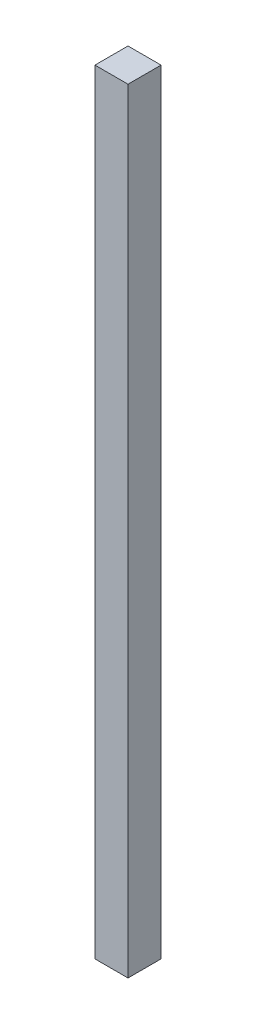
SolidWorks part; units mm, degrees
ref_plane "Front Plane" through (0, 0, 0) normal (0, 0, 1) x (1, 0, 0)
ref_plane "Top Plane" through (0, 0, 0) normal (0, 1, 0) x (1, 0, 0)
ref_plane "Right Plane" through (0, 0, 0) normal (1, 0, 0) x (0, 0, -1)
sketch "Sketch1" plane through (0, 0, 0) normal (0, 1, 0) x (1, 0, 0)
  line L1 (0, 0) -> (25.4, 0)
  line L2 (0, 0) -> (0, 25.4)
  line L3 (0, 25.4) -> (25.4, 25.4)
  line L4 (25.4, 0) -> (25.4, 25.4)
  dimension "D1" = 25.4
  dimension "D2" = 25.4
extrude "Boss-Extrude1" add sketch "Sketch1" along normal blind 609.6
sketch "Sketch3" plane through (0, 0, -25.4) normal (0, 0, -1) x (-1, 0, 0)
  line L0 (0, 609.6) -> (0, 0) construction
  line L1 (0, 484.3268) -> (-25.4, 484.3268)
  line L2 (0, 484.3268) -> (0, 609.6)
  line L3 (0, 609.6) -> (-25.4, 609.6)
  line L4 (-25.4, 484.3268) -> (-25.4, 609.6)
  line L5 (0, 484.3268) -> (-25.4, 484.3268) construction
extrude "Cut-Extrude1" [suppressed] cut sketch "Sketch3" against normal up to surface (25.4 mm away) up to face at (12.7, 304.8, 0)
sketch "Sketch4" [suppressed] plane through (0, 0, 0) normal (0, 0, 1) x (1, 0, 0)
  line L0 (0, 609.6) -> (0, 0) construction
  line L1 (0, 297.6179) -> (25.4, 297.6179)
  line L2 (0, 297.6179) -> (0, 609.6)
  line L3 (0, 609.6) -> (25.4, 609.6)
  line L4 (25.4, 297.6179) -> (25.4, 609.6)
  line L5 (25.4, 297.6179) -> (0, 297.6179) construction
extrude "Cut-Extrude2" [suppressed] cut sketch "Sketch4" against normal up to surface (25.4 mm away) up to face at (12.7, 304.8, -25.4)
sketch "Sketch5" plane through (0, 0, -25.4) normal (0, 0, -1) x (-1, 0, 0)
  line L0 (0, 609.6) -> (0, 0) construction
  line L1 (0, 594.529) -> (-25.4, 594.529)
  line L2 (0, 594.529) -> (0, 609.6)
  line L3 (0, 609.6) -> (-25.4, 609.6)
  line L4 (-25.4, 594.529) -> (-25.4, 609.6)
  line L5 (0, 594.529) -> (-25.4, 594.529) construction
extrude "Cut-Extrude3" cut sketch "Sketch5" against normal up to surface (25.4 mm away) up to face at (12.7, 304.8, 0)
sketch "Sketch6" [suppressed] plane through (0, 0, -25.4) normal (0, 0, -1) x (-1, 0, 0)
  line L0 (0, 609.6) -> (0, 0) construction
  line L1 (0, 574.651) -> (-25.4, 574.651)
  line L2 (0, 574.651) -> (0, 609.6)
  line L3 (0, 609.6) -> (-25.4, 609.6)
  line L4 (-25.4, 574.651) -> (-25.4, 609.6)
  line L5 (0, 574.651) -> (-25.4, 574.651) construction
extrude "Cut-Extrude4" [suppressed] cut sketch "Sketch6" against normal up to surface (25.4 mm away) up to face at (12.7, 297.2645, 0)
sketch "Sketch7" [suppressed] plane through (0, 0, 0) normal (0, 0, 1) x (1, 0, 0)
  line L0 (25.4, 609.6) -> (25.4, 0) construction
  line L1 (25.4, 443.1645) -> (0, 443.1645)
  line L2 (25.4, 443.1645) -> (25.4, 609.6)
  line L3 (25.4, 609.6) -> (0, 609.6)
  line L4 (0, 443.1645) -> (0, 609.6)
  line L5 (25.4, 443.1645) -> (0, 443.1645) construction
extrude "Cut-Extrude5" [suppressed] cut sketch "Sketch7" against normal up to surface (25.4 mm away) up to face at (12.7, 297.2645, -25.4)
sketch "Sketch8" [suppressed] plane through (0, 0, -25.4) normal (0, 0, -1) x (-1, 0, 0)
  line L0 (0, 609.6) -> (0, 0) construction
  line L1 (0, 340.2572) -> (-25.4, 340.2572)
  line L2 (0, 340.2572) -> (0, 609.6)
  line L3 (0, 609.6) -> (-25.4, 609.6)
  line L4 (-25.4, 340.2572) -> (-25.4, 609.6)
  line L5 (0, 340.2572) -> (-25.4, 340.2572) construction
extrude "Cut-Extrude6" [suppressed] cut sketch "Sketch8" against normal up to surface (25.4 mm away) up to face at (12.7, 297.2645, 0)
sketch "Sketch9" [suppressed] plane through (0, 0, 0) normal (0, 0, 1) x (1, 0, 0)
  line L0 (0, 609.6) -> (0, 0) construction
  line L1 (0, 350.8333) -> (25.4, 350.8333)
  line L2 (0, 350.8333) -> (0, 609.6)
  line L3 (0, 609.6) -> (25.4, 609.6)
  line L4 (25.4, 350.8333) -> (25.4, 609.6)
  line L5 (25.4, 350.8333) -> (0, 350.8333) construction
extrude "Cut-Extrude7" [suppressed] cut sketch "Sketch9" against normal up to surface (25.4 mm away) up to face at (12.7, 297.2645, -25.4)
